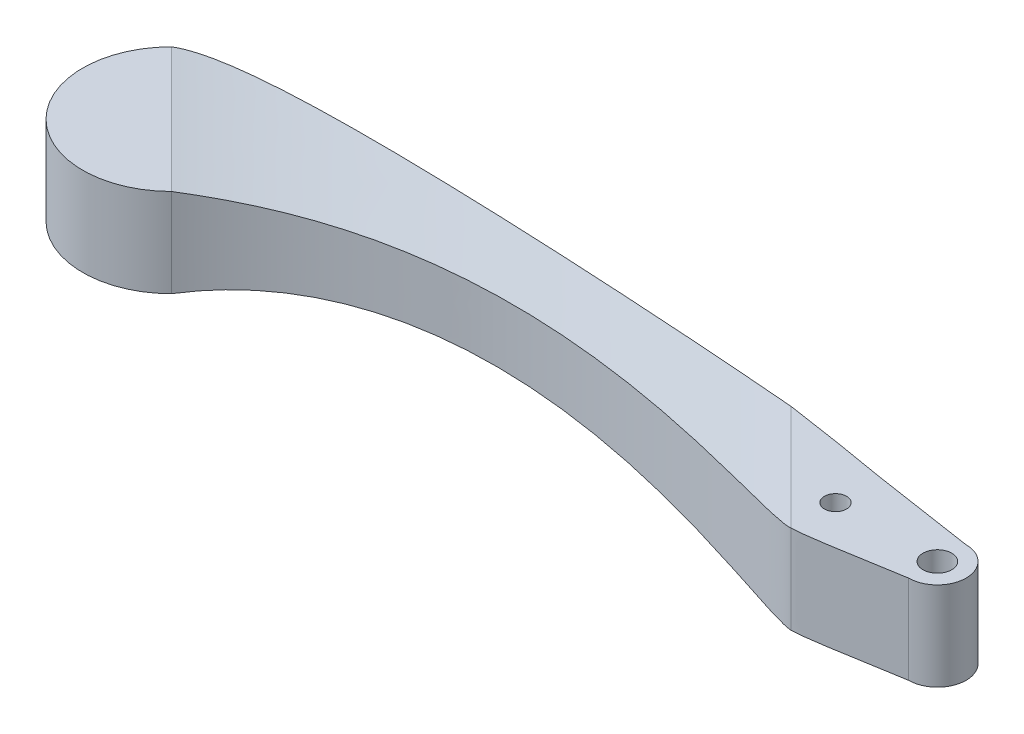
SolidWorks part; units mm, degrees
ref_plane "Front Plane" through (0, 0, 0) normal (0, 0, 1) x (1, 0, 0)
ref_plane "Top Plane" through (0, 0, 0) normal (0, 1, 0) x (1, 0, 0)
ref_plane "Right Plane" through (0, 0, 0) normal (1, 0, 0) x (0, 0, -1)
sketch "Sketch1" plane through (0, 0, 0) normal (0, 1, 0) x (1, 0, 0)
  line L0 (0, 0) -> (-300, 0) construction
  line L1 (0, 0) -> (46, 0) construction
  line L2 (-300, 0) -> (-300, 40) construction
  line L3 (-328.2843, 28.2843) -> (-271.7157, -28.2843) construction
  circle A0 centre (0, 0) radius 5
  circle A1 centre (46, 0) radius 6.5
  circle A2 centre (-300, 0) radius 40
  circle A3 centre (0, 0) radius 20
  circle A4 centre (46, 0) radius 13
  spline S0 degree 3 poles (-271.7157, -28.2843) (-189.2199, 54.2115) (-20, -20) (0, -20) knots 0 0 0 0 1 1 1 1
  spline S1 degree 3 poles (-328.2843, 28.2843) (-300, 56.5685) (-114.8731, 40.3783) (0, 20) knots 0 0 0 0 1 1 1 1
  spline S2 degree 2 poles (0, -20) (5.9085, -20) (46, -13) knots 0 0 0 1 1 1
  spline S3 degree 2 poles (0, 20) (0.0315, 20) (46, 13) knots 0 0 0 1 1 1
  dimension "D3" = 10
  dimension "D4" = 13
  dimension "D5" = 80
  dimension "D6" = 40
  dimension "D7" = 45
  dimension "D8" = 120
  dimension "D9" = 350
  dimension "D10" = 350
  dimension "D11" = 60
  dimension "D12" = 26
  dimension "D1" = 46
  dimension "D2" = 300
extrude "Boss-Extrude1" add sketch "Sketch1" along normal blind 20 and the other way blind 20 contours S1 A2 | S1 A2 S0 A3 | S3 A3 S0 A0 | S3 A3 S2 A4 | A4 A1 region at (-299.9271, 0, 0.2395) region at (-151.7179, 0, -19.1123) region at (-19.1932, 0, -3.0516) region at (26.0397, 0, 0.3418) region at (54.9324, 0, -8.9324)
ref_plane "Plane1" through (-121.7157, 0, -121.7157) normal (0.7071, 0, 0.7071) x (0, 1, 0)
sketch "Sketch3" plane through (-71.2994, 0, -172.132) normal (0.7071, 0, 0.7071) x (0.7071, 0, -0.7071)
  line L0 (-2.323, 174.4861) -> (-2.323, -69.6609) construction
  line L1 (-283.4315, 0) -> (16.5685, 0) construction
  line L2 (-283.4315, -20) -> (-85.4416, -20)
  line L3 (-283.4315, -20) -> (-283.4315, 20) construction
  line L6 (-283.4315, -20) -> (-283.4315, 20)
  line L7 (-323.4315, -20) -> (-283.4315, -20) construction
  line L8 (-283.4315, 20) -> (-323.4315, 20) construction
  line L9 (-283.4315, 20) -> (-85.4416, 20)
  spline S0 degree 3 poles (-283.4315, 20) (-227.5434, 10.6387) (-151.7177, 12.7946) (-85.4416, 20) knots 0 0 0 0 1 1 1 1
  spline S1 degree 3 poles (-283.4315, -20) (-227.5434, -10.6387) (-151.7177, -12.7946) (-85.4416, -20) knots 0 0 0 0 1 1 1 1
  point P13 (20.6196, 0)
  point P14 (-283.4315, 0)
  point P17 (16.5685, 0)
  dimension "D3" = 200
  dimension "D1" = 300
  dimension "D2" = 170
extrude "Cut-Extrude2" cut sketch "Sketch3" against normal through all and the other way through all contours S1 L2 | L9 S0 region at (-204.6414, -17.4956, -38.79)
